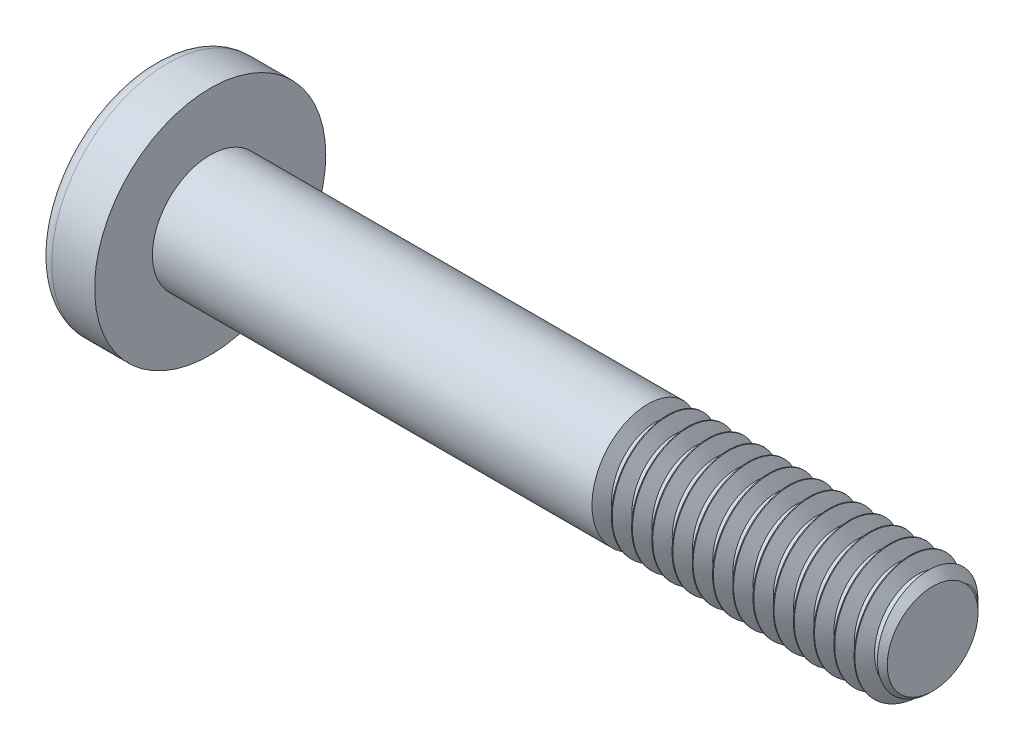
SolidWorks part; units mm, degrees
material "Plain Carbon Steel"
ref_plane "Front Plane" through (0, 0, 0) normal (0, 0, 1) x (1, 0, 0)
ref_plane "Top Plane" through (0, 0, 0) normal (0, 1, 0) x (1, 0, 0)
ref_plane "Right Plane" through (0, 0, 0) normal (1, 0, 0) x (0, 0, -1)
sketch "Sketch1" plane through (0, 0, 0) normal (0, 1, 0) x (1, 0, 0)
  line L0 (-11.9, 2) -> (-11.9, 4)
  line L3 (13.1, 0) -> (-15, 0)
  line L4 (-11.9, 2) -> (13.1, 2)
  line L5 (13.1, 2) -> (13.1, 0)
  line L6 (-13.3836, 4) -> (-11.9, 4)
  arc A0 (-13.773, 3.8007) -> (-15, 0) centre (-8.5, 0) ccw
  arc A1 (-13.773, 3.8007) -> (-13.3836, 4) centre (-13.3836, 3.52) cw
  dimension "D5" = 6.5
  dimension "D6" = 0.48
  dimension "D2" = 25
  dimension "D3" = 3.1
revolve "Revolve1" add sketch "Sketch1" angle 360 about L3
chamfer "Chamfer1" distance 0.4295 angle 45 1 edges at (13.1, 0, -2)
ref_plane "Plane1" through (13.8, 0, 0) normal (1, 0, 0) x (0, 0, -1)
sketch "Sketch2" plane through (13.8, 0, 0) normal (1, 0, 0) x (0, 0, -1)
  circle A2 centre (0, 0) radius 1.5705 construction
  circle A3 centre (0, 0) radius 1.5705
curve "Helix/Spiral1" pitch 0.7 height 10.7 radius 1.5705 centre (13.8, 0, 0) axis (-1, 0, 0) start towards (0, 0, -1)
sketch "Sketch3" plane through (0, 0, 0) normal (0, 1, 0) x (1, 0, 0)
  line L0 (12.6705, 2) -> (-11.9, 2) construction
  line L1 (12.6705, 2) -> (-3.0595, 2) construction
  line L3 (13.8, -1.5705) -> (13.8, 1.5705) construction
  line L4 (13.4571, 2.0128) -> (14.1429, 2.0128)
  line L5 (14.1429, 2.0128) -> (13.8875, 1.5705)
  line L6 (13.4571, 2.0128) -> (13.7125, 1.5705)
  line L7 (13.8875, 1.5705) -> (13.7125, 1.5705)
  line L8 (13.8, -1.5705) -> (13.8, 1.5705) construction
  point P11 (13.8, 2.0128)
  point P13 (13.8, 1.5705)
  dimension "D1" = 60
  dimension "D2" = 0.4295
  dimension "D3" = 0.175
sweep "Cut-Sweep1" cut profiles "Sketch3" path "Helix/Spiral1" align with end faces yes
ref_plane "Plane2" through (-15, 0, 0) normal (-1, 0, 0) x (0, 0, 1)
sketch "Sketch4" plane through (-15, 0, 0) normal (-1, 0, 0) x (0, 0, 1)
  line L0 (0.465, -2.2) -> (-0.465, -2.2)
  line L1 (0.465, -2.2) -> (0.465, 2.2)
  line L2 (-0.465, 2.2) -> (0.465, 2.2)
  line L3 (-0.465, 2.2) -> (-0.465, -2.2)
  point P4 (0, 2.2)
  point P5 (0.465, 0)
  point P7 (-0.465, 0)
  point P8 (0, -2.2)
  point P9 (0, 0)
  dimension "D1" = 4.4
  dimension "D2" = 0.93
ref_plane "Plane3" through (-12.583, 0, 0) normal (-1, 0, 0) x (0, 0, 1)
sketch "Sketch5" plane through (-12.583, 0, 0) normal (-1, 0, 0) x (0, 0, 1)
  line L0 (0.2325, -0.2325) -> (-0.2325, -0.2325)
  line L1 (0.2325, -0.2325) -> (0.2325, 0.2325)
  line L2 (-0.2325, 0.2325) -> (0.2325, 0.2325)
  line L3 (-0.2325, 0.2325) -> (-0.2325, -0.2325)
  point P4 (0, 0)
  dimension "D1" = 0.465
  dimension "D2" = 0.465
loft "Cut-Loft1" cut profiles "Sketch5", "Sketch4" connector at (-12.583, -0.2325, -0.2325) connector at (-15, -2.2, -0.465)
pattern_circular "CirPattern1" count 2 every 90 about axis through (13.1, 0, 0) along (1, 0, 0) of "Cut-Loft1"
